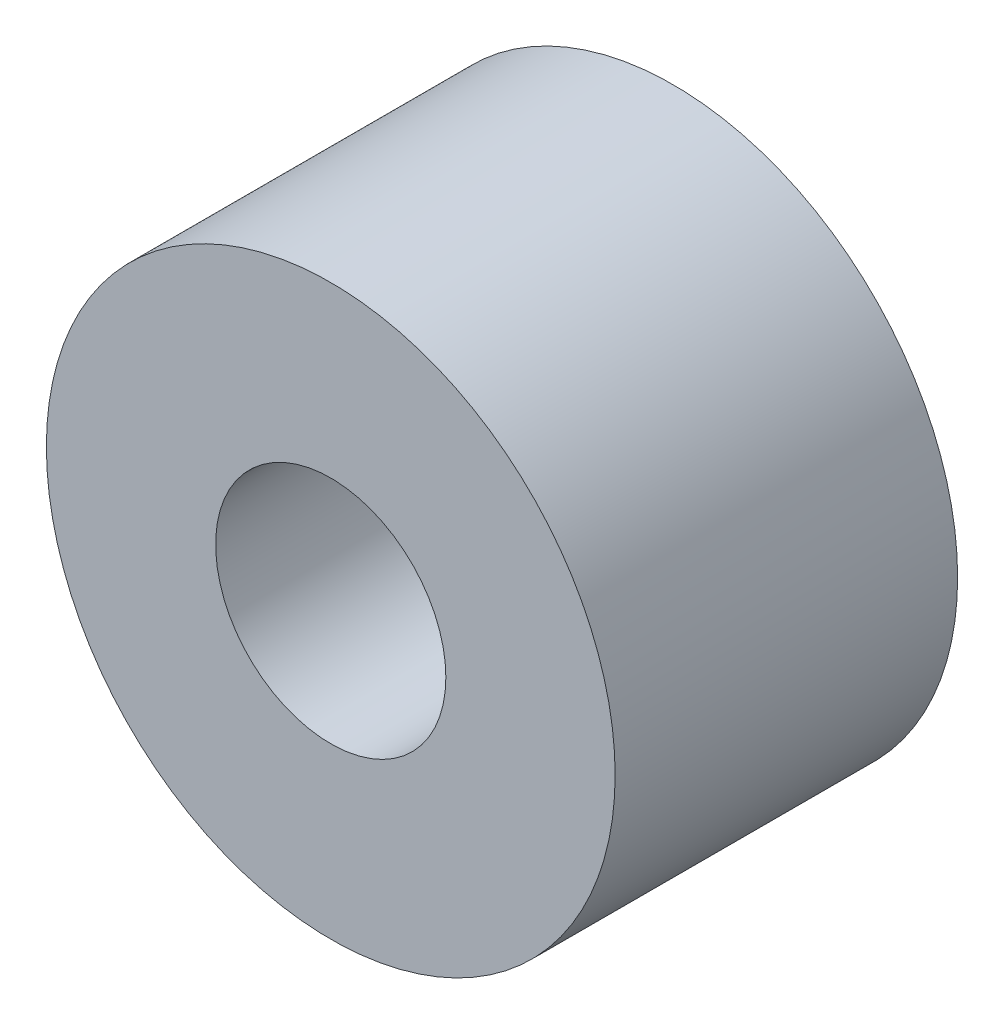
SolidWorks part; units mm, degrees
ref_plane "Front Plane" through (0, 0, 0) normal (0, 0, 1) x (1, 0, 0)
ref_plane "Top Plane" through (0, 0, 0) normal (0, 1, 0) x (1, 0, 0)
ref_plane "Right Plane" through (0, 0, 0) normal (1, 0, 0) x (0, 0, -1)
sketch "Sketch1" plane through (0, 0, 0) normal (0, 1, 0) x (1, 0, 0)
  line L0 (2.125, -3.75) -> (5.25, -3.75)
  line L1 (5.25, -3.75) -> (5.25, 0)
  line L2 (5.25, 0) -> (2.125, 0)
  line L3 (2.125, 0) -> (2.125, -3.75)
  line L4 (0, 0) -> (0, -3.75) construction
  dimension "D1" = 2.125
  dimension "D2" = 5.25
  dimension "D3" = 3.75
revolve "Revolve1" add sketch "Sketch1" angle 360 about L4 reverse direction yes
sketch "Sketch2" plane through (0, 0, 3.75) normal (0, 0, 1) x (1, 0, 0)
  circle A0 centre (0, 0) radius 2.125
  circle A1 centre (0, 0) radius 5.25
  dimension "D1" = 4.25
  dimension "D2" = 10.5
extrude "Boss-Extrude1" add sketch "Sketch2" along normal blind 3.0725
sketch "Sketch3" plane through (0, 0, 0) normal (0, 0, -1) x (-1, 0, 0)
  circle A0 centre (0, 0) radius 3
  circle A1 centre (0, 0) radius 5.25
  circle A2 centre (0, 0) radius 5.25
  dimension "D2" = 6
  dimension "D1" = 0
extrude "Cut-Extrude1" cut sketch "Sketch3" against normal blind 0.5
